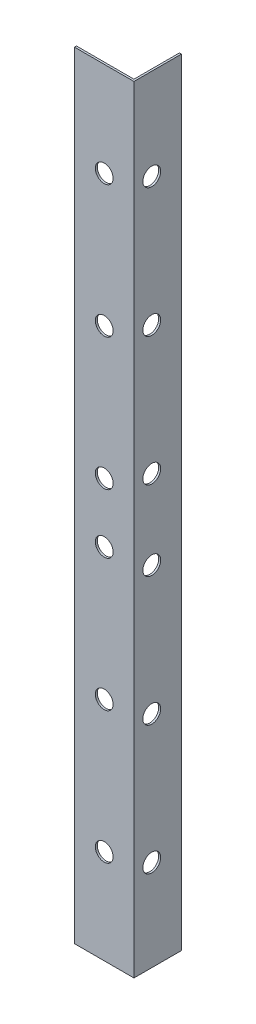
SolidWorks part; units mm, degrees
material "6061-T6 (SS)"
ref_plane "Alzado" through (0, 0, 0) normal (0, 0, 1) x (1, 0, 0)
ref_plane "Planta" through (0, 0, 0) normal (0, 1, 0) x (1, 0, 0)
ref_plane "Vista lateral" through (0, 0, 0) normal (1, 0, 0) x (0, 0, -1)
sketch "Sketch1" plane through (0, 0, 0) normal (0, 1, 0) x (1, 0, 0)
  line L0 (0, 0) -> (15, 0)
  line L1 (15, 0) -> (15, 12)
  line L2 (15, 12) -> (14.5, 12)
  line L3 (14.5, 12) -> (14.5, 0.5)
  line L4 (14.5, 0.5) -> (0, 0.5)
  line L5 (0, 0.5) -> (0, 0)
  dimension "D1" = 15
  dimension "D2" = 12
  dimension "D3" = 0.5
  dimension "D4" = 0.5
extrude "Boss-Extrude1" add sketch "Sketch1" along normal blind 196
sketch "Sketch4" plane through (0, 0, 0) normal (0, 0, 1) x (1, 0, 0)
  line L0 (15, 196) -> (15, 0) construction
  line L1 (0, 196) -> (15, 196)
  line L2 (0, 196) -> (0, 193)
  line L3 (0, 193) -> (15, 193)
  line L4 (15, 196) -> (15, 193)
  line L6 (0, 0) -> (15, 0)
  line L7 (0, 0) -> (0, 3)
  line L8 (0, 3) -> (15, 3)
  line L9 (15, 0) -> (15, 3)
  dimension "D1" = 3
  dimension "D2" = 3
extrude "Cut-Extrude3" [suppressed] cut sketch "Sketch4" against normal up to next
sketch "Sketch5" plane through (15, 0, 0) normal (1, 0, 0) x (0, 0, -1)
  circle A0 centre (4.5, 23) radius 2.25
  circle A1 centre (4.5, 55.5) radius 2.25
  circle A2 centre (4.5, 88) radius 2.25
  circle A3 centre (4.5, 108) radius 2.25
  circle A4 centre (4.5, 140.5) radius 2.25
  circle A5 centre (4.5, 173) radius 2.25
  dimension "D1" = 4.5
extrude "Cut-Extrude4" cut sketch "Sketch5" against normal up to next
sketch "Sketch6" plane through (0, 0, 0) normal (0, 0, 1) x (1, 0, 0)
  circle A0 centre (7.5, 23.8333) radius 2.25
  circle A1 centre (7.5, 57.1667) radius 2.25
  circle A2 centre (7.5, 90.5) radius 2.25
  circle A3 centre (7.5, 105.5) radius 2.25
  circle A4 centre (7.5, 138.8333) radius 2.25
  circle A5 centre (7.5, 172.1667) radius 2.25
  dimension "D1" = 4.5
extrude "Cut-Extrude5" cut sketch "Sketch6" against normal up to next
